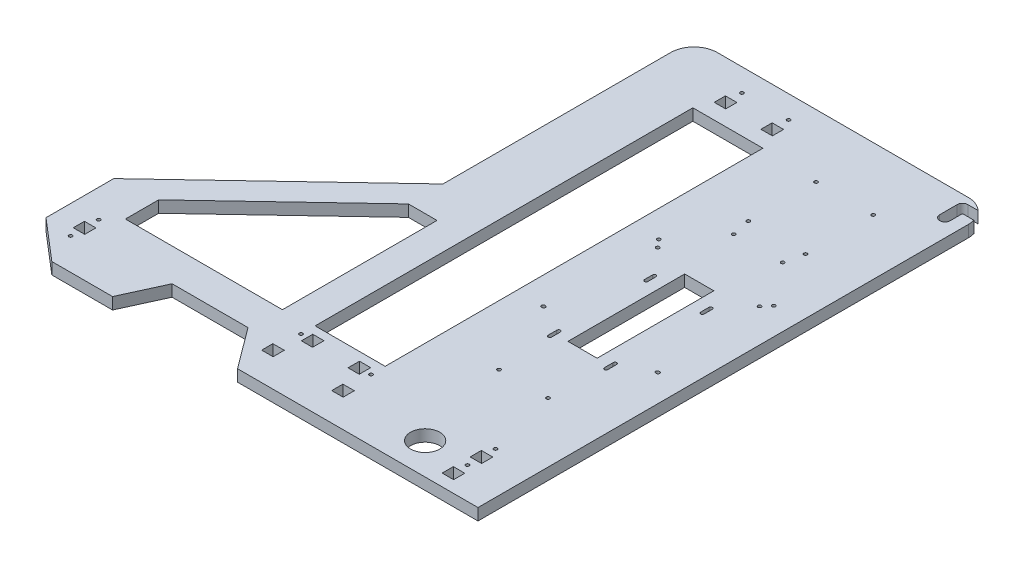
SolidWorks part; units mm, degrees
ref_plane "Front Plane" through (0, 0, 0) normal (0, 0, 1) x (1, 0, 0)
ref_plane "Top Plane" through (0, 0, 0) normal (0, 1, 0) x (1, 0, 0)
ref_plane "Right Plane" through (0, 0, 0) normal (1, 0, 0) x (0, 0, -1)
sketch "Sketch1" plane through (0, 0, 0) normal (0, 1, 0) x (1, 0, 0)
  line L0 (0, 0) -> (-235, 0)
  line L1 (-235, 0) -> (-235, -215)
  line L2 (-235, -215) -> (-380, -352)
  line L3 (-380, -352) -> (-380, -410)
  line L4 (-380, -410) -> (-345, -440)
  line L5 (-345, -440) -> (-293, -440)
  line L6 (-293, -440) -> (-277, -405)
  line L7 (-277, -405) -> (-212, -405)
  line L8 (-212, -405) -> (-185.9255, -440)
  line L9 (-185.9255, -440) -> (0, -440)
  line L10 (0, 0) -> (0, -440)
  line L12 (-293, -440) -> (-185.9255, -440) construction
  dimension "D3" = 235
  dimension "D5" = 58
  dimension "D13" = 190
  dimension "D7" = 35
  dimension "D2" = 126.686
  dimension "D11" = 65
  dimension "D15" = 52
  dimension "D12" = 30
  dimension "D10" = 35
  dimension "D14" = 16
  dimension "D6" = 380
  dimension "D4" = 440
extrude "Boss-Extrude1" add sketch "Sketch1" along normal blind 10
sketch "Sketch16" plane through (0, 10, 0) normal (0, 1, 0) x (1, 0, 0)
  line L0 (0, -440) -> (20, -440)
  line L1 (20, -440) -> (20, 0)
  line L2 (20, 0) -> (0, 0)
  line L3 (0, 0) -> (0, -440)
  dimension "D1" = 20
  dimension "D2" = 90
extrude "Boss-Extrude2" add sketch "Sketch16" against normal through all
sketch "Sketch2" plane through (0, 10, 0) normal (0, 1, 0) x (1, 0, 0)
  line L0 (-235, -215) -> (-235, -405) construction
  line L1 (-277, -405) -> (-212, -405) construction
  line L2 (-345, -440) -> (-345, -318.931) construction
  line L3 (-235, -215) -> (-380, -352) construction
  line L4 (-345, -348.5097) -> (-235, -244.5787)
  line L5 (-235, -244.5787) -> (-210.5, -244.5787)
  line L6 (-210.5, -244.5787) -> (-210.5, -377)
  line L7 (-210.5, -377) -> (-345, -377)
  line L8 (-345, -377) -> (-345, -348.5097)
  line L9 (0, -440) -> (0, 0) construction
  line L10 (-184.5, -375) -> (-124.5, -375)
  line L11 (-184.5, -375) -> (-184.5, -51.45)
  line L12 (-184.5, -51.45) -> (-124.5, -51.45)
  line L13 (-124.5, -375) -> (-124.5, -51.45)
  line L14 (-124.5, -387.1) -> (-184.5, -387.1) construction
  line L15 (-16, -440) -> (-16, 0) construction
  line L16 (20, 0) -> (-235, 0) construction
  line L17 (-355.95, -430.6143) -> (-355.95, -329.2769) construction
  line L18 (-20.9, -429.8) -> (-11.1, -429.8)
  line L19 (-20.9, -429.8) -> (-20.9, -420.2)
  line L20 (-20.9, -420.2) -> (-11.1, -420.2)
  line L21 (-11.1, -429.8) -> (-11.1, -420.2)
  line L22 (-20.9, -429.8) -> (-11.1, -420.2) construction
  line L23 (-20.9, -420.2) -> (-11.1, -429.8) construction
  line L24 (-20.9, -405.8) -> (-11.1, -405.8)
  line L25 (-20.9, -405.8) -> (-20.9, -396.2)
  line L26 (-20.9, -396.2) -> (-11.1, -396.2)
  line L27 (-11.1, -405.8) -> (-11.1, -396.2)
  line L28 (-20.9, -405.8) -> (-11.1, -396.2) construction
  line L29 (-20.9, -396.2) -> (-11.1, -405.8) construction
  line L30 (-380, -410) -> (-345, -440) construction
  line L32 (-351.05, -396.2) -> (-360.85, -396.2)
  line L33 (-351.05, -396.2) -> (-351.05, -405.8)
  line L34 (-351.05, -405.8) -> (-360.85, -405.8)
  line L35 (-360.85, -396.2) -> (-360.85, -405.8)
  line L36 (-351.05, -396.2) -> (-360.85, -405.8) construction
  line L37 (-351.05, -405.8) -> (-360.85, -396.2) construction
  line L38 (-185.9255, -440) -> (20, -440) construction
  line L39 (-185.9255, -440) -> (20, -440) construction
  line L40 (-173.724, -33.45) -> (-113.724, -33.45) construction
  line L41 (-154.5, -51.45) -> (-154.5, -33.45) construction
  line L42 (-179.4, -28.65) -> (-169.6, -28.65)
  line L43 (-179.4, -28.65) -> (-179.4, -38.25)
  line L44 (-179.4, -38.25) -> (-169.6, -38.25)
  line L45 (-169.6, -28.65) -> (-169.6, -38.25)
  line L46 (-179.4, -28.65) -> (-169.6, -38.25) construction
  line L47 (-179.4, -38.25) -> (-169.6, -28.65) construction
  line L48 (-129.6, -38.25) -> (-139.4, -28.65) construction
  line L49 (-129.6, -28.65) -> (-139.4, -38.25) construction
  line L50 (-139.4, -28.65) -> (-139.4, -38.25)
  line L51 (-129.6, -38.25) -> (-139.4, -38.25)
  line L52 (-129.6, -28.65) -> (-129.6, -38.25)
  line L53 (-129.6, -28.65) -> (-139.4, -28.65)
  line L54 (-174.5, -33.45) -> (-174.5, -19.45) construction
  line L55 (-134.5, -33.45) -> (-134.5, -19.45) construction
  line L56 (-154.5, -375) -> (-154.5, -440) construction
  line L57 (-174.5, -387.1) -> (-134.5, -387.1) construction
  line L58 (-129.7, -392) -> (-139.3, -382.2) construction
  line L59 (-179.3, -382.2) -> (-169.7, -382.2)
  line L60 (-179.3, -382.2) -> (-179.3, -392)
  line L61 (-179.3, -392) -> (-169.7, -392)
  line L62 (-169.7, -382.2) -> (-169.7, -392)
  line L63 (-179.3, -382.2) -> (-169.7, -392) construction
  line L64 (-179.3, -392) -> (-169.7, -382.2) construction
  line L65 (-129.7, -382.2) -> (-139.3, -392) construction
  line L66 (-139.3, -382.2) -> (-139.3, -392)
  line L67 (-129.7, -392) -> (-139.3, -392)
  line L68 (-129.7, -382.2) -> (-129.7, -392)
  line L69 (-129.7, -382.2) -> (-139.3, -382.2)
  line L70 (-119.6, -415.9) -> (-129.4, -406.3) construction
  line L71 (-189.4, -406.3) -> (-179.6, -406.3)
  line L72 (-189.4, -406.3) -> (-189.4, -415.9)
  line L73 (-189.4, -415.9) -> (-179.6, -415.9)
  line L74 (-179.6, -406.3) -> (-179.6, -415.9)
  line L75 (-189.4, -406.3) -> (-179.6, -415.9) construction
  line L76 (-189.4, -415.9) -> (-179.6, -406.3) construction
  line L77 (-119.6, -406.3) -> (-129.4, -415.9) construction
  line L78 (-129.4, -406.3) -> (-129.4, -415.9)
  line L79 (-119.6, -415.9) -> (-129.4, -415.9)
  line L80 (-119.6, -406.3) -> (-119.6, -415.9)
  line L81 (-119.6, -406.3) -> (-129.4, -406.3)
  line L82 (-360.85, -396.2) -> (-11.1, -396.2) construction
  circle A0 centre (-16, -413) radius 1.45
  circle A1 centre (-16, -389) radius 1.45
  circle A2 centre (-355.95, -413) radius 1.45
  circle A3 centre (-355.95, -389) radius 1.45
  circle A4 centre (-174.5, -19.45) radius 1.45
  circle A5 centre (-134.5, -19.45) radius 1.45
  circle A6 centre (-124.5, -387.1) radius 1.45
  circle A7 centre (-184.5, -387.1) radius 1.45
  point P25 (-16, -425)
  point P30 (-16, -401)
  point P44 (-355.95, -401)
  point P61 (-174.5, -33.45)
  point P72 (-134.5, -33.45)
  point P85 (-174.5, -387.1)
  point P94 (-134.5, -387.1)
  point P95 (-184.5, -411.1)
  point P104 (-124.5, -411.1)
  point P105 (-154.5, -387.1)
  dimension "D13" = 2.9
  dimension "D14" = 2.9
  dimension "D23" = 2.9
  dimension "D24" = 2.9
  dimension "D31" = 2.9
  dimension "D37" = 2.9
  dimension "D1" = 21.5
  dimension "D2" = 28
  dimension "D3" = 24.5
  dimension "D4" = 60
  dimension "D7" = 26
  dimension "D8" = 9.6
  dimension "D9" = 9.8
  dimension "D10" = 9.8
  dimension "D11" = 9.6
  dimension "D12" = 24
  dimension "D15" = 24
  dimension "D19" = 9.8
  dimension "D20" = 9.6
  dimension "D26" = 12
  dimension "D27" = 9.8
  dimension "D28" = 9.6
  dimension "D33" = 9.6
  dimension "D38" = 9.8
  dimension "D39" = 9.6
  dimension "D41" = 24
  dimension "D34" = 30
  dimension "D36" = 12.1
  dimension "D30" = 18
  dimension "D29" = 40
  dimension "D17" = 15
  dimension "D32" = 14
  dimension "D35" = 20
  dimension "D16" = 12
  dimension "D21" = 90
  dimension "D25" = 24
  dimension "D5" = 353.75
  dimension "D22" = 349.75
  dimension "D40" = 30
  dimension "D6" = 65
  dimension "D42" = 0
  dimension "D43" = 0
  dimension "D18" = 16
  dimension "D44" = 9.8
extrude "Cut-Extrude1" cut sketch "Sketch2" against normal through all
fillet "Fillet1" radius 20 2 edges at (-235, 5, 0) (20, 5, 0)
sketch "Sketch11" plane through (0, 10, 0) normal (0, 1, 0) x (1, 0, 0)
  line L0 (-124.5, -213.225) -> (20, -213.225) construction
  line L1 (20, -440) -> (20, -20) construction
  line L3 (-52.25, -213.225) -> (-52.25, -440) construction
  line L6 (-124.5, -375) -> (-124.5, -51.45) construction
  line L8 (-185.9255, -440) -> (20, -440) construction
  circle A0 centre (-52.25, -413) radius 12.5
  circle A1 centre (-16, -413) radius 1.45 construction
  dimension "D1" = 25
  dimension "D2" = 0
  dimension "D3" = 0
extrude "WiringHole" cut sketch "Sketch11" against normal through all
sketch "Sketch9" [suppressed] plane through (0, 10, 0) normal (0, 1, 0) x (1, 0, 0)
  line L0 (-52.25, -400.5) -> (-52.25, 0) construction
  line L1 (0, 0) -> (-215, 0) construction
  line L2 (-124.5, -213.225) -> (20, -213.225) construction
  line L3 (-124.5, -375) -> (-124.5, -51.45) construction
  line L4 (-4.75, -124.725) -> (-4.75, -301.725) construction
  line L6 (-99.75, -124.725) -> (-4.75, -124.725) construction
  line L7 (-4.75, -301.725) -> (-99.75, -301.725) construction
  line L8 (-99.75, -301.725) -> (-99.75, -124.725) construction
  line L9 (20, -440) -> (20, -20) construction
  circle A0 centre (-52.25, -413) radius 12.5 construction
  circle A1 centre (-99.75, -124.725) radius 1.45
  circle A2 centre (-4.75, -124.725) radius 1.45
  circle A3 centre (-4.75, -301.725) radius 1.45
  circle A4 centre (-99.75, -301.725) radius 1.45
  dimension "D3" = 2.9
  dimension "D4" = 2.9
  dimension "D1" = 95
  dimension "D2" = 177
  dimension "D5" = 47.5
extrude "MountingHoles-PSU" [suppressed] cut sketch "Sketch9" against normal through all
sketch "Sketch10" plane through (0, 10, 0) normal (0, 1, 0) x (1, 0, 0)
  line L0 (-124.5, -213.225) -> (20, -213.225) construction
  line L1 (20, -440) -> (20, -20) construction
  line L2 (-64.75, -228.225) -> (-39.75, -228.225) construction
  line L3 (-52.25, -213.225) -> (-52.25, 0) construction
  line L7 (-124.5, -375) -> (-124.5, -51.45) construction
  line L8 (-64.75, -278.225) -> (-39.75, -278.225)
  line L9 (-64.75, -278.225) -> (-64.75, -178.225)
  line L10 (-64.75, -178.225) -> (-39.75, -178.225)
  line L11 (-39.75, -278.225) -> (-39.75, -178.225)
  line L12 (-64.75, -278.225) -> (-39.75, -178.225) construction
  line L13 (-64.75, -178.225) -> (-39.75, -278.225) construction
  line L15 (0, 0) -> (-215, 0) construction
  line L17 (-52.25, -213.225) -> (-52.25, -440) construction
  line L18 (-185.9255, -440) -> (20, -440) construction
  line L19 (-64.75, -213.225) -> (-39.75, -213.225) construction
  line L20 (-52.25, -278.225) -> (-52.25, -178.225) construction
  dimension "D1" = 25
  dimension "D2" = 100
  dimension "D3" = 0
  dimension "D4" = 0
  dimension "D5" = 0
  dimension "D6" = 15
extrude "WiringSlot" cut sketch "Sketch10" against normal through all
sketch "CenterLines" plane through (0, 10, 0) normal (0, 1, 0) x (1, 0, 0)
  line L0 (-52.25, -278.225) -> (-52.25, -178.225) construction
  line L1 (-64.75, -278.225) -> (-39.75, -278.225) construction
  line L2 (-39.75, -178.225) -> (-64.75, -178.225) construction
  line L3 (-64.75, -228.225) -> (-39.75, -228.225) construction
  line L4 (-64.75, -178.225) -> (-64.75, -278.225) construction
  line L5 (-39.75, -278.225) -> (-39.75, -178.225) construction
ref_plane "Plane1" through (-52.25, 0, 0) normal (1, 0, 0) x (0, 0, -1)
sketch "Sketch6" plane through (0, 10, 0) normal (0, 1, 0) x (1, 0, 0)
  line L0 (-52.25, -278.225) -> (-52.25, -178.225) construction
  line L1 (-76.35, -237.075) -> (-28.15, -237.075) construction
  line L2 (-28.15, -192.625) -> (-28.15, -275.125) construction
  line L3 (-64.75, -278.225) -> (-39.75, -278.225) construction
  line L4 (-64.75, -245.925) -> (-39.75, -245.925) construction
  line L5 (-39.75, -178.225) -> (-64.75, -178.225) construction
  line L6 (-28.15, -192.625) -> (-28.15, -199.625) construction
  line L7 (-26.7, -192.625) -> (-26.7, -199.625)
  line L8 (-29.6, -192.625) -> (-29.6, -199.625)
  line L9 (-64.75, -228.225) -> (-39.75, -228.225) construction
  line L10 (-64.75, -178.225) -> (-64.75, -278.225) construction
  line L11 (-39.75, -278.225) -> (-39.75, -178.225) construction
  line L12 (-28.15, -282.125) -> (-28.15, -275.125) construction
  line L13 (-29.6, -282.125) -> (-29.6, -275.125)
  line L14 (-76.35, -274.525) -> (-76.35, -199.625) construction
  line L15 (-28.15, -282.125) -> (-28.15, -199.625) construction
  line L16 (-26.7, -282.125) -> (-26.7, -275.125)
  arc A2 (-26.7, -192.625) -> (-29.6, -192.625) centre (-28.15, -192.625) ccw
  arc A3 (-29.6, -199.625) -> (-26.7, -199.625) centre (-28.15, -199.625) ccw
  circle A4 centre (-76.35, -274.525) radius 1.45
  circle A6 centre (-76.35, -199.625) radius 1.45
  arc A8 (-29.6, -282.125) -> (-26.7, -282.125) centre (-28.15, -282.125) ccw
  arc A9 (-26.7, -275.125) -> (-29.6, -275.125) centre (-28.15, -275.125) ccw
  point P20 (-28.15, -196.125)
  point P25 (-28.15, -278.625)
  dimension "D8" = 2.9
  dimension "D12" = 2.9
  dimension "D4" = 1.45
  dimension "D5" = 1.45
  dimension "D11" = 82.5
  dimension "D14" = 74.9
  dimension "D2" = 24.1
  dimension "D3" = 48.2
  dimension "D6" = 8.85
  dimension "D9" = 7
  dimension "D10" = 7
extrude "MountingHoles-RAMPS" cut sketch "Sketch6" against normal through all
mirror "Mirror1" about plane through (-52.25, 0, 0) normal (1, 0, 0) of "MountingHoles-RAMPS"
sketch "Sketch5" plane through (0, 10, 0) normal (0, 1, 0) x (1, 0, 0)
  line L0 (-39.75, -228.225) -> (-64.75, -228.225) construction
  line L3 (-39.75, -278.225) -> (-39.75, -178.225) construction
  line L5 (-64.75, -178.225) -> (-64.75, -278.225) construction
  line L7 (-31.25, -127.725) -> (-73.25, -127.725) construction
  line L8 (-31.25, -328.725) -> (-73.25, -328.725) construction
  line L9 (-52.25, -228.225) -> (-52.25, -127.725) construction
  line L10 (-52.25, -228.225) -> (-52.25, -328.725) construction
  circle A0 centre (-73.25, -127.725) radius 1.45
  circle A1 centre (-31.25, -127.725) radius 1.45
  circle A2 centre (-31.25, -328.725) radius 1.45
  circle A3 centre (-73.25, -328.725) radius 1.45
  point P17 (-52.25, -127.725)
  point P22 (-52.25, -328.725)
  dimension "D2" = 2.9
  dimension "D5" = 2.9
  dimension "D6" = 2.9
  dimension "D7" = 2.9
  dimension "D3" = 201
  dimension "D4" = 100.5
  dimension "D8" = 21
  dimension "D9" = 21
  dimension "D10" = 100.5
extrude "MountingHoles-Melzi" cut sketch "Sketch5" against normal through all
sketch "Sketch13" plane through (0, 0, 0) normal (0, -1, 0) x (-1, 0, 0)
  line L0 (64.75, -213.225) -> (124.5, -213.225) construction
  line L1 (124.5, -375) -> (124.5, -51.45) construction
  line L2 (101.46, -262.74) -> (101.46, -163.71) construction
  line L3 (52.25, -278.225) -> (52.25, -178.225) construction
  line L4 (64.75, -178.225) -> (64.75, -278.225) construction
  line L6 (101.46, -262.74) -> (3.56, -262.74) construction
  circle A0 centre (101.46, -163.71) radius 1.45
  circle A1 centre (101.46, -262.74) radius 1.45
  circle A2 centre (8.62, -170.19) radius 1.45
  circle A3 centre (3.56, -262.74) radius 1.45
  point P11 (101.46, -213.225)
  dimension "D8" = 2.9
  dimension "D6" = 2.9
  dimension "D1" = 2.9
  dimension "D2" = 49.515
  dimension "D3" = 49.21
  dimension "D4" = 6.48
  dimension "D5" = 92.84
  dimension "D7" = 97.9
extrude "Mountingholes-Smoothieboard" cut sketch "Sketch13" against normal through all
mirror "Flipped" about plane through (-52.25, 0, 0) normal (1, 0, 0) of "Mountingholes-Smoothieboard"
sketch "Sketch21" plane through (0, 10, 0) normal (0, 1, 0) x (1, 0, 0)
  line L0 (-52.25, -178.225) -> (-52.25, 0) construction
  line L1 (-39.75, -178.225) -> (-64.75, -178.225) construction
  line L2 (0, 0) -> (-215, 0) construction
  line L3 (-52.25, -82.725) -> (-23.3697, -82.725) construction
  circle A0 centre (-27.75, -53.725) radius 1.45
  circle A1 centre (-76.75, -53.725) radius 1.45
  circle A2 centre (-76.75, -111.725) radius 1.45
  circle A3 centre (-27.75, -111.725) radius 1.45
  circle A4 centre (-31.25, -127.725) radius 1.45 construction
  dimension "D1" = 2.9
  dimension "D2" = 24.5
  dimension "D3" = 29
  dimension "D4" = 45
extrude "Pi" cut sketch "Sketch21" against normal through all
sketch "Sketch17" plane through (0, 10, 0) normal (0, 1, 0) x (1, 0, 0)
  line L0 (0, 0) -> (20, 0) construction
  line L1 (20, -23.6361) -> (20, 0) construction
  line L2 (20, -440) -> (20, -20) construction
  line L3 (20, -10) -> (5, -10) construction
  line L4 (20, -14.5) -> (5, -14.5)
  line L5 (20, -5.5) -> (5, -5.5)
  arc A0 (20, -14.5) -> (20, -5.5) centre (20, -10) ccw
  arc A1 (5, -5.5) -> (5, -14.5) centre (5, -10) ccw
  point P8 (12.5, -10)
  dimension "D1" = 9
  dimension "D2" = 15
  dimension "D3" = 10
extrude "Cut-Extrude3" cut sketch "Sketch17" against normal through all
sketch "Sketch18" plane through (0, 10, 0) normal (0, 1, 0) x (1, 0, 0)
  line L0 (5, -5.5) -> (5, -14.5) construction
  line L1 (0.5, -10) -> (5, -10) construction
  line L2 (5, -10) -> (5, -25) construction
  line L3 (9.5, -10) -> (9.5, -25)
  line L4 (0.5, -10) -> (0.5, -25)
  arc A0 (5, -5.5) -> (5, -14.5) centre (5, -10) ccw construction
  arc A1 (9.5, -10) -> (0.5, -10) centre (5, -10) ccw
  arc A2 (0.5, -25) -> (9.5, -25) centre (5, -25) ccw
  point P10 (5, -17.5)
  dimension "D1" = 9
  dimension "D2" = 0
  dimension "D3" = 15
extrude "Cut-Extrude4" cut sketch "Sketch18" against normal through all
sketch "Sketch19" plane through (0, 10, 0) normal (0, 1, 0) x (1, 0, 0)
  line L0 (-5, -25) -> (15, -25) construction
  line L1 (5, -25) -> (5, -5.5) construction
  circle A0 centre (15, -25) radius 1.45
  arc A1 (5, -5.5) -> (0.5, -10) centre (5, -10) ccw construction
  circle A2 centre (-5, -25) radius 1.45
  dimension "D2" = 2.9
extrude "Cut-Extrude5" [suppressed] cut sketch "Sketch19" against normal through all
equation "\"Y-ROD-SPACING\"=75"
equation "\"Y-BED-OFFSET\"=2"
equation "\"Y-BED-ROD-INSET\"=3.5"
equation "\"T-SLOT-NUT-FILLET-RADIUS\"=0.5"
equation "\"T-SLOT-SCREW-SHAFT-RADIUS\"=1.55"
equation "\"T-SLOT-SCREW-SHAFT-CUTOUT-LENGTH\"=11.0"
equation "\"T-SLOT-NUT-DEPTH\"=3.5"
equation "\"T-SLOT-NUT-WIDTH\"=2.85"
equation "\"T-SLOT-NUT-END-DISTANCE\"=8"
equation "\"ACRYLIC-TAB-CUTOUT-SIZE\"=\"ACRYLIC-THICKNESS\"+\"ACRYLIC-TAB-TOLERANCE\"*2"
equation "\"ACRYLIC-TAB-WIDTH\"=\"ACRYLIC-THICKNESS\""
equation "\"ACRYLIC-M3-HOLE\"=2.9"
equation "\"SMOOTHROD-CAP-SCREW-DISTANCE\"=20"
equation "\"FRAME-WIDTH-INNER\"=370"
equation "\"D24@Sketch2\"=\"ACRYLIC-M3-HOLE\""
equation "\"D23@Sketch2\"=\"ACRYLIC-M3-HOLE\""
equation "\"D19@Sketch2\"=\"ACRYLIC-THICKNESS\"-\"KERF\"*2"
equation "\"D20@Sketch2\"=\"ACRYLIC-TAB-WIDTH\"-\"KERF\"*4"
equation "\"D37@Sketch2\"=\"ACRYLIC-M3-HOLE\""
equation "\"D33@Sketch2\"=\"ACRYLIC-TAB-WIDTH\"-\"KERF\"*4"
equation "\"D38@Sketch2\"=\"ACRYLIC-THICKNESS\"-\"KERF\"*2"
equation "\"D39@Sketch2\"=\"ACRYLIC-TAB-WIDTH\"-\"KERF\"*4"
equation "\"D13@Sketch2\"=\"ACRYLIC-M3-HOLE\""
equation "\"D14@Sketch2\"=\"ACRYLIC-M3-HOLE\""
equation "\"D8@Sketch2\"=\"ACRYLIC-TAB-WIDTH\"-\"KERF\"*4"
equation "\"D9@Sketch2\"=\"ACRYLIC-THICKNESS\"-\"KERF\"*2"
equation "\"D10@Sketch2\"=\"ACRYLIC-THICKNESS\"-\"KERF\"*2"
equation "\"D11@Sketch2\"=\"ACRYLIC-TAB-WIDTH\"-\"KERF\"*4"
equation "\"D31@Sketch2\"=\"ACRYLIC-M3-HOLE\""
equation "\"D27@Sketch2\"=\"ACRYLIC-THICKNESS\"-\"KERF\"*2"
equation "\"D28@Sketch2\"=\"ACRYLIC-TAB-WIDTH\"-\"KERF\"*4"
equation "\"NEMA17-HOLE-SPACING\"=31"
equation "\"NEMA17-CENTRAL-CUTOUT\"=22.5"
equation "\"Z-BRACKET-REACH\"=55"
equation "\"TOP-BRACKET-SPACING\"=40"
equation "\"D29@Sketch2\"=\"TOP-BRACKET-SPACING\""
equation "\"ACRYLIC-THICKNESS\"=10"
equation "\"SMOOTHROD-Z-LENGTH\"=350"
equation "\"D5@Sketch2\"=\"SMOOTHROD-Z-LENGTH\"-\"SMOOTHROD-TIGHTENING-HEADROOM\"+4"
equation "\"SMOOTHROD-X-LENGTH\"=350"
equation "\"SMOOTHROD-Y-LENGTH\"=350"
equation "\"D22@Sketch2\"=\"SMOOTHROD-Y-LENGTH\"-\"SMOOTHROD-TIGHTENING-HEADROOM\""
equation "\"SMOOTHROD-TIGHTENING-HEADROOM\"=.25"
equation "\"X-ROD-SPACING\"=45"
equation "\"Z-ROD-SPACING\"=17.5"
equation "\"LEADSCREW-Z-LENGTH\"=300"
equation "\"SCREW-HEAD-RADIUS\"=6"
equation "\"PRINTED-X-SMOOTHROD-DIAMETER\"=9.0"
equation "\"PRINTED-X-SMOOTHROD-CUTOUT\"=10"
equation "\"PRINTED-X-BASE-HEIGHT\"=10"
equation "\"PRINTED-LM8UU-CUTOUT-SIZE\"=15.5"
equation "\"PRINTED-LM8UU-CUTOUT-LENGTH\"=24.5"
equation "\"PRINTED-X-IDLER-HEIGHT\"=16"
equation "\"PSU-MOUNTING-WIDTH\"=95"
equation "\"PSU-MOUNTING-HEIGHT\"=177"
equation "\"D1@Sketch9\"=\"PSU-MOUNTING-WIDTH\""
equation "\"D3@Sketch9\"=\"ACRYLIC-M3-HOLE\""
equation "\"D1@Boss-Extrude1\"=\"ACRYLIC-THICKNESS\""
equation "\"D6@Sketch1\"=\"SMOOTHROD-Y-LENGTH\"+30"
equation "\"D4@Sketch9\"=\"ACRYLIC-M3-HOLE\""
equation "\"D2@Sketch9\"=\"PSU-MOUNTING-HEIGHT\""
equation "\"D5@Sketch9\"=\"PSU-MOUNTING-WIDTH\"/2"
equation "\"D4@Sketch1\"=\"SMOOTHROD-Z-LENGTH\"+90"
equation "\"D8@Sketch6\"=\"ACRYLIC-M3-HOLE\""
equation "\"D12@Sketch6\"=\"ACRYLIC-M3-HOLE\""
equation "\"D2@Sketch5\"=\"ACRYLIC-M3-HOLE\""
equation "\"D5@Sketch5\"=\"ACRYLIC-M3-HOLE\""
equation "\"D6@Sketch5\"=\"ACRYLIC-M3-HOLE\""
equation "\"D7@Sketch5\"=\"ACRYLIC-M3-HOLE\""
equation "\"D1@Sketch13\"=\"ACRYLIC-M3-HOLE\""
equation "\"D6@Sketch13\"=\"ACRYLIC-M3-HOLE\""
equation "\"D8@Sketch13\"=\"ACRYLIC-M3-HOLE\""
equation "\"D4@Sketch6\"=\"ACRYLIC-M3-HOLE\"/2"
equation "\"D5@Sketch6\"=\"ACRYLIC-M3-HOLE\"/2"
equation "\"Y-BED-SCREW-SPACING\"=209"
equation "\"Y-BED-SCREW-CUTOUT-SLOT-HEIGHT\"=2"
equation "\"ACRYLIC-THICKNESS2\"=4.5"
equation "\"ACRYLIC-TAB-TOLERANCE\"=-.05"
equation "\"Z-ROD-INSET\"=16"
equation "\"SCREW-LENGTH-FRAME\"=\"ACRYLIC-THICKNESS\" + 10"
equation "\"SCREW-LENGTH-MOTOR\"=\"ACRYLIC-THICKNESS\" + 5"
equation "\"SCREW-LENGTH-EXTRUDER\"=28"
equation "\"Y-BELT-TO-ROD-DISTANCE\"=20"
equation "\"SPOOL-HOLDER-ROD-SPACING\"=150"
equation "\"ACRYLIC-X-CARRIAGE-WIDTH\"=55"
equation "\"ACRYLIC-X-CARRIAGE-HEIGHT\"=75"
equation "\"ACRYLIC-X-CARRIAGE-LM8UU-CUTOUT-WIDTH\"=24.25"
equation "\"ACRYLIC-X-CARRIAGE-SCREW-SPACING-X\"=15"
equation "\"ACRYLIC-X-CARRIAGE-SCREW-SPACING-Y\"=33"
equation "\"ACRYLIC-X-CARRIAGE-CENTER-TAB-SPACING\"=14"
equation "\"ACRYLIC-X-CARRIAGE-EXTRUDER-OFFSET\"=26"
equation "\"ACRYLIC-X-CARRIAGE-EXTRUDER-ANGLE\"=90"
equation "\"ACRYLIC-X-CARRIAGE-EXTRUDER-SHELF-DEPTH\"=\"ACRYLIC-X-CARRIAGE-EXTRUDER-OFFSET\" + 28"
equation "\"ACRYLIC-X-CARRIAGE-EXTRUDER-BRACE-SPACING\"=23"
equation "\"ACRYLIC-X-CARRIAGE-EXTRUDER-BRACE-TAB-OFFSET\"=20"
equation "\"ACRYLIC-X-CARRIAGE-EXTRUDER-BRACE-HEIGHT\"=35"
equation "\"ACRYLIC-X-CARRIAGE-EXTRUDER-BRACE-SCREW-SPACING\"=22"
equation "\"D1@Sketch19\"=\"SMOOTHROD-CAP-SCREW-DISTANCE\"/2"
equation "\"D2@Sketch19\"=\"ACRYLIC-M3-HOLE\""
equation "\"D1@Sketch21\"=\"ACRYLIC-M3-HOLE\""
equation "\"KERF\"=0.1"
equation "\"PRINTED-M3-HOLE\"=3.5"
equation "\"PRINTED-M3-NUT-AF\"=6.25"
equation "\"ACRYLIC-X-CARRIAGE-LM8UU-CUTOUT-HEIGHT\"=11.0"
equation "\"ACRYLIC-X-CARRIAGE-DUAL-WIDTH-MULTIPLIER\"=1.65"
equation "\"ACRYLIC-X-CARRIAGE-DUAL-HOTEND-SPACING\"=42"
equation "\"ACRYLIC-X-CARRIAGE-DUAL-WIDTH\"=75"
equation "\"ACRYLIC-X-CARRIAGE-DUAL-FAN-OFFSET\"=52"
equation "\"ACRYLIC-X-CARRIAGE-DUAL-FAN-HEIGHT\"=20"
equation "\"ACRYLIC-X-CARRIAGE-DUAL-HOTEND-SEPARATION\"=36"
equation "\"ACRYLIC-X-CARRIAGE-DUAL-MOUNT-PLATE-DEPTH\"=75"
equation "\"ACRYLIC-X-CARRIAGE-DUAL-MOUNT-BRACE-WIDTH\"=33"
equation "\"ACRYLIC-X-CARRIAGE-DUAL-MOUNT-SCREW-WIDTH\"=40"
equation "\"BLOWER-FAN-WIDTH\"=15"
equation "\"D44@Sketch2\"=\"ACRYLIC-THICKNESS\"-\"KERF\"*2"
